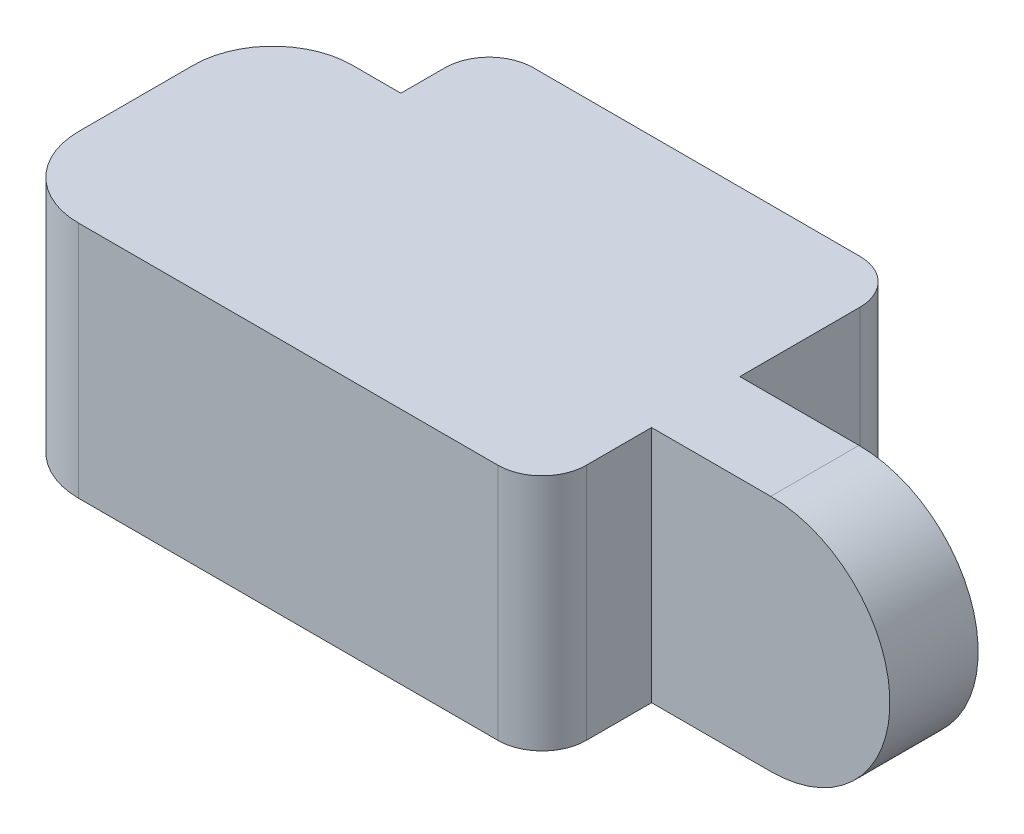
SolidWorks part; units mm, degrees
ref_plane "Front Plane" through (0, 0, 0) normal (0, 0, 1) x (1, 0, 0)
ref_plane "Top Plane" through (0, 0, 0) normal (0, 1, 0) x (1, 0, 0)
ref_plane "Right Plane" through (0, 0, 0) normal (1, 0, 0) x (0, 0, -1)
sketch "Sketch1" plane through (0, 0, 0) normal (0, 1, 0) x (1, 0, 0)
  line L0 (-1000, 0) -> (49000, 0) construction
  line L1 (-34.29, -12.7) -> (34.29, -12.7)
  line L2 (-34.29, 12.7) -> (34.29, 12.7)
  line L3 (34.29, 12.7) -> (34.29, -12.7)
  line L8 (0, -1000) -> (0, 49000) construction
  line L20 (-34.29, 47.244) -> (-34.29, 12.7)
  line L22 (-46.99, 59.944) -> (-140.97, 59.944)
  line L23 (-153.67, 47.244) -> (-153.67, 34.544)
  line L24 (-190.5, 11.684) -> (-190.5, -21.336)
  line L25 (-153.67, 34.544) -> (-167.64, 34.544)
  line L27 (-46.99, -44.196) -> (-167.64, -44.196)
  line L28 (-34.29, -12.7) -> (-34.29, -31.496)
  arc A5 (-46.99, 59.944) -> (-34.29, 47.244) centre (-46.99, 47.244) cw
  arc A6 (-140.97, 59.944) -> (-153.67, 47.244) centre (-140.97, 47.244) ccw
  arc A7 (-167.64, -44.196) -> (-190.5, -21.336) centre (-167.64, -21.336) cw
  arc A8 (-167.64, 34.544) -> (-190.5, 11.684) centre (-167.64, 11.684) ccw
  arc A9 (-34.29, -31.496) -> (-46.99, -44.196) centre (-46.99, -31.496) cw
  dimension "D5" = 104.14
  dimension "D7" = 18.796
  dimension "D13" = 12.7
  dimension "D11" = 12.7
  dimension "D15" = 22.86
  dimension "D16" = 12.7
  dimension "D18" = 22.86
  dimension "D2" = 34.29
  dimension "D3" = 68.58
  dimension "D4" = 78.74
  dimension "D9" = 12.7
  dimension "D10" = 25.4
  dimension "D14" = 119.38
  dimension "D17" = 190.5
extrude "Boss-Extrude1" add sketch "Sketch1" along normal blind 34.29 and the other way blind 34.29
sketch "Sketch2" plane through (0, 0, 0) normal (0, 0, 1) x (1, 0, 0)
  line L3 (0, 34.29) -> (44.29, 34.29)
  line L4 (44.29, 34.29) -> (44.29, -34.29)
  line L5 (44.29, -34.29) -> (0, -34.29)
  line L6 (34.29, -34.29) -> (34.29, 34.29) construction
  arc A0 (0, -34.29) -> (0, 34.29) centre (0, 0) ccw
  dimension "D1" = 10
extrude "Cut-Extrude1" cut sketch "Sketch2" against normal through all and the other way through all
sketch3d "3DSketch1"
  line L0 (0, 0, 127) -> (0, 0, -127)
  point P3 (0, 0, 0)
  dimension "D1" = 254
